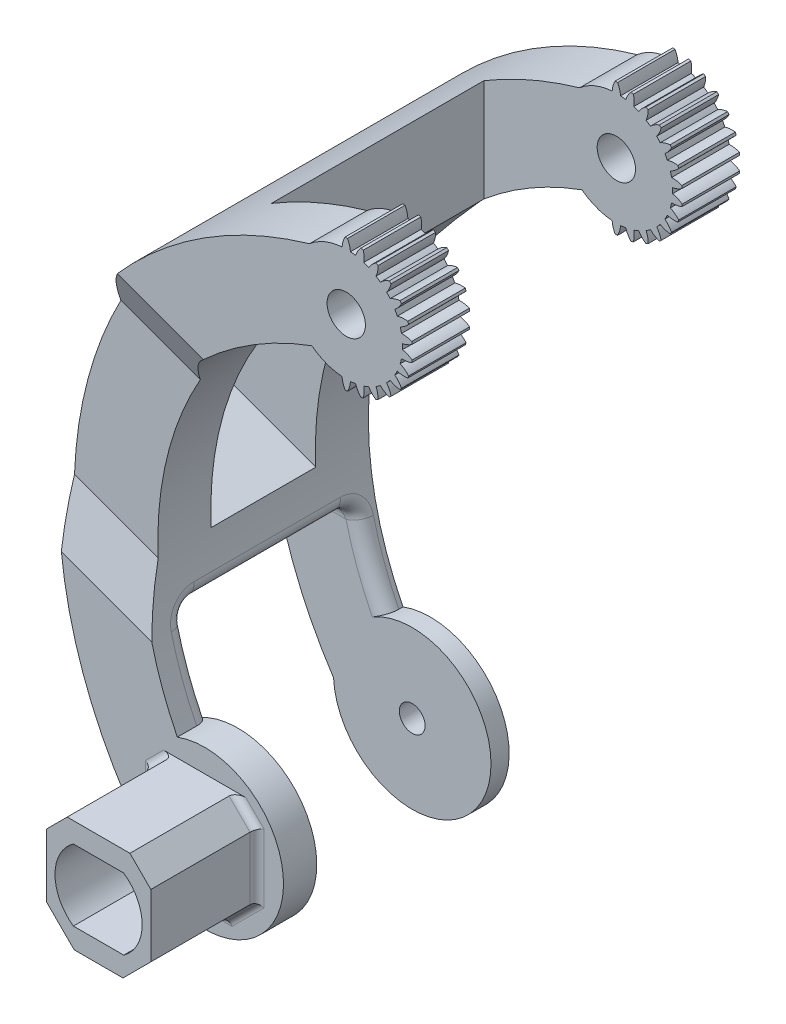
SolidWorks part; units mm, degrees
ref_plane "Alzado" through (0, 0, 0) normal (0, 0, 1) x (1, 0, 0)
ref_plane "Planta" through (0, 0, 0) normal (0, 1, 0) x (1, 0, 0)
ref_plane "Vista lateral" through (0, 0, 0) normal (1, 0, 0) x (0, 0, -1)
sketch "General" plane through (0, 0, 0) normal (0, 0, 1) x (1, 0, 0)
  line L0 (0, -33.4233) -> (0, 47689.0306) construction
  line L1 (6.6907, 0) -> (47729.1446, 0) construction
  line L2 (-11, 14) -> (-11, -14) construction
  line L3 (-23, 14) -> (23, 14) construction
  line L4 (-23, 14) -> (-23, -14) construction
  line L5 (-23, -14) -> (23, -14) construction
  line L6 (23, 14) -> (23, -14) construction
  line L7 (-23, 14) -> (23, -14) construction
  line L8 (-23, -14) -> (23, 14) construction
  line L9 (-53.8528, 23.512) -> (-38.6411, 23.4646) construction
  line L10 (-53.8528, 23.512) -> (-54.1389, 38.7648) construction
  line L11 (-53.8528, 23.512) -> (-42.0695, 24.391) construction
  line L12 (-53.8528, 23.512) -> (-42.0757, 22.5533) construction
  line L13 (-53.8528, 23.512) -> (-42.1693, 21.747) construction
  line L14 (-53.8528, 23.512) -> (-39.8274, 23.7032) construction
  line L15 (-53.8528, 23.512) -> (-39.829, 23.226) construction
  line L16 (0, -50) -> (-37.5362, -81.4966) construction
  line L103 (-42.0757, 22.5533) -> (-40.8989, 22.7984) construction
  line L104 (-39.829, 23.226) -> (-39.8274, 23.7032) construction
  line L105 (-40.8944, 24.138) -> (-42.0695, 24.391) construction
  circle A0 centre (0, -50) radius 30 construction
  circle A1 centre (-53.8528, 23.512) radius 14.0267 construction
  circle A2 centre (-53.8528, 23.512) radius 11.8161 construction
  circle A3 centre (-53.8528, 23.512) radius 12.9735 construction
  circle A4 centre (-11, 0) radius 11 construction
  circle A5 centre (11, 0) radius 11 construction
  circle A6 centre (-37.5362, -81.4966) radius 19 construction
  arc A109 (-42.1693, 21.747) -> (-42.0757, 22.5533) centre (-53.8528, 23.512) ccw construction
  arc A110 (-40.8989, 22.7984) -> (-39.829, 23.226) centre (-41.5742, 26.0406) ccw construction
  arc A111 (-39.8274, 23.7032) -> (-40.8944, 24.138) centre (-41.5916, 20.9005) ccw construction
  arc A112 (-42.0695, 24.391) -> (-42.1576, 25.198) centre (-53.8528, 23.512) ccw construction
  point P30 (0, 0)
  dimension "D1" = 60
  dimension "D8" = 23.6322
  dimension "D9" = 25.947
  dimension "D10" = 28.0535
  dimension "D12" = 22
  dimension "D13" = 38
  dimension "D2" = 50
  dimension "D3" = 28
  dimension "D4" = 12
  dimension "D5" = 46
  dimension "D6" = 12.857
  dimension "D7" = 8.92
  dimension "D11" = 4.445
  dimension "D14" = 130
sketch "dientes left" plane through (0, 0, 0) normal (0, 0, 1) x (1, 0, 0)
  line L0 (0, -33.4233) -> (0, 47689.0306) construction
  line L1 (-11, 4.2518) -> (-11, 18009.3981) construction
  line L2 (-52.3069, -19.6337) -> (-41.0879, -19.8625) construction
  line L9 (-53.8528, 23.512) -> (-38.6411, 23.4646) construction
  line L10 (35.2249, 36.7395) -> (32.3069, 26.491) construction
  line L11 (-53.8528, 23.512) -> (-42.0695, 24.391) construction
  line L12 (-53.8528, 23.512) -> (-42.0757, 22.5533) construction
  line L13 (-53.8528, 23.512) -> (-42.1693, 21.747) construction
  line L14 (-53.8528, 23.512) -> (-39.8274, 23.7032) construction
  line L15 (-53.8528, 23.512) -> (-39.829, 23.226) construction
  line L16 (-41.9402, -19.1329) -> (-42.8803, -18.9305) construction
  line L17 (-52.3069, -19.6337) -> (-52.5358, -7.4315) construction
  line L18 (-52.3069, -19.6337) -> (-42.8803, -18.9305) construction
  line L19 (-52.3069, -19.6337) -> (-41.0866, -19.4807) construction
  line L20 (-42.8852, -20.4007) -> (-41.9438, -20.2046) construction
  line L21 (-52.3069, -19.6337) -> (-40.1376, -19.6716) construction
  line L22 (-41.0879, -19.8625) -> (-41.0866, -19.4807) construction
  line L23 (-52.3069, -19.6337) -> (-42.9601, -21.0457) construction
  line L24 (-52.3069, -19.6337) -> (-42.8852, -20.4007) construction
  line L25 (-11, -8.8667) -> (-7.1144, -7.4524) construction
  line L26 (-11, -8.8667) -> (-14.6616, -7.5339) construction
  line L28 (-11, 0) -> (-11, 9.5) construction
  line L29 (-11, 0) -> (-13.8497, -7.8295) construction
  line L33 (-11, 0) -> (-8.1503, -7.8295) construction
  line L34 (-11, -8.8667) -> (-5.7586, -8.8667) construction
  line L35 (-11.4974, -8.6856) -> (-10.5026, -8.6856) construction
  line L103 (-42.0757, 22.5533) -> (-40.8989, 22.7984) construction
  line L104 (-39.829, 23.226) -> (-39.8274, 23.7032) construction
  line L105 (-40.8944, 24.138) -> (-42.0695, 24.391) construction
  line L106 (32.3069, 26.491) -> (37.8505, 37.0466) construction
  line L107 (32.3069, 26.491) -> (37.6564, 34.9915) construction
  line L108 (37.6564, 34.9915) -> (37.934, 35.9748) construction
  line L109 (37.8505, 37.0466) -> (38.032, 36.9492) construction
  line L110 (32.3069, 26.491) -> (42.3228, 27.2382) construction
  line L111 (32.3069, 26.491) -> (32.0638, 39.4559) construction
  line L112 (32.3069, 26.491) -> (42.2379, 24.9907) construction
  line L113 (36.9768, 35.383) -> (37.6564, 34.9915) construction
  line L114 (32.3069, 26.491) -> (38.032, 36.9492) construction
  line L115 (-11, 14) -> (-11, -14) construction
  circle A1 centre (-53.8528, 23.512) radius 14.0267 construction
  circle A2 centre (-53.8528, 23.512) radius 11.8161 construction
  circle A3 centre (-53.8528, 23.512) radius 12.9735 construction
  arc A7 (-41.0866, -19.4807) -> (-41.9402, -19.1329) centre (-42.498, -21.7229) ccw construction
  circle A8 centre (-52.3069, -19.6337) radius 11.2214 construction
  arc A9 (-42.8803, -18.9305) -> (-42.9508, -18.2849) centre (-52.3069, -19.6337) ccw construction
  circle A10 centre (-52.3069, -19.6337) radius 10.3788 construction
  arc A11 (-42.9601, -21.0457) -> (-42.8852, -20.4007) centre (-52.3069, -19.6337) ccw construction
  arc A12 (-41.9438, -20.2046) -> (-41.0879, -19.8625) centre (-42.484, -17.6108) ccw construction
  circle A13 centre (-52.3069, -19.6337) radius 9.4529 construction
  circle A17 centre (-11, 0) radius 8.8667 construction
  circle A20 centre (-11, 0) radius 8.075
  circle A47 centre (32.3069, 26.491) radius 11.0275 construction
  arc A48 (37.934, 35.9748) -> (38.032, 36.9492) centre (35.2249, 36.7395) ccw construction
  circle A49 centre (32.3069, 26.491) radius 11.9227 construction
  circle A50 centre (32.3069, 26.491) radius 10.0437 construction
  arc A109 (-42.1693, 21.747) -> (-42.0757, 22.5533) centre (-53.8528, 23.512) ccw construction
  arc A110 (-40.8989, 22.7984) -> (-39.829, 23.226) centre (-41.5742, 26.0406) ccw construction
  arc A111 (-39.8274, 23.7032) -> (-40.8944, 24.138) centre (-41.5916, 20.9005) ccw construction
  arc A112 (-42.0695, 24.391) -> (-42.1576, 25.198) centre (-53.8528, 23.512) ccw construction
  arc A113 (-11.598, -8.0528) -> (-11.1753, -9.4984) centre (-8.1503, -7.8295) ccw
  arc A115 (-10.8247, -9.4984) -> (-10.402, -8.0528) centre (-13.8497, -7.8295) ccw
  circle A116 centre (-11, 0) radius 9.5
  point P54 (32.3206, 26.4908)
  point P195 (-10.9863, -0.0002)
  point P220 (-11, 0)
  dimension "D8" = 23.6322
  dimension "D9" = 25.947
  dimension "D10" = 28.0535
  dimension "D2" = 16.15
  dimension "D3" = 17.7333
  dimension "D4" = 19
  dimension "D6" = 12.857
  dimension "D7" = 8.92
  dimension "D11" = 4.445
  dimension "D12" = 0.99
  dimension "D13" = 4.475
  dimension "D14" = 11.815
  dimension "D15" = 10.6558
  dimension "D5" = 20
  dimension "D16" = 20
  dimension "D17" = 0.9948
sketch "Cilindro" plane through (0, 0, 0) normal (0, 0, 1) x (1, 0, 0)
  circle A0 centre (-11, 0) radius 8.075
  dimension "D1" = 16.15
extrude "Saliente-Extruir2" add sketch "Cilindro" along normal mid plane 47
extrude "Saliente-Extruir3" add sketch "dientes left" along normal through all and the other way through all contours A116 A115 A20 A113 region at (-11, -8.6709, 0)
pattern_circular "CirPattern1" count 14 over 180 about axis through (-11, 0, 23.5) along (0, 0, 1) of "Saliente-Extruir3"
sketch "Croquis5" plane through (0, 0, 0) normal (0, 0, 1) x (1, 0, 0)
  line L0 (-11, 14) -> (-11, -14) construction
  line L1 (-16.2713, 6.1171) -> (-11, -4.8934)
  arc A0 (-11, -4.8934) -> (-41.4607, -70.8953) centre (0, -50) ccw
  arc A1 (-16.2713, 6.1171) -> (-48.8248, -82.094) centre (0, -50) ccw
  circle A2 centre (-37.5362, -81.4966) radius 11.3044 construction
  circle A3 centre (-37.5362, -81.4966) radius 1.8517
  arc A4 (-48.8248, -82.094) -> (-41.4607, -70.8953) centre (-37.5362, -81.4966) ccw
  arc A6 (-11.598, 8.0528) -> (-11.598, -8.0528) centre (-11, 0) ccw construction
  dimension "D1" = 12
extrude "Saliente-Extruir4" add sketch "Croquis5" along normal up to surface and the other way up to surface up to face at (-5.9627, 0, 23.5) other way up to face at (-5.9627, 0, -23.5)
sketch "Croquis10" plane through (0, 0, 23.5) normal (0, 0, 1) x (1, 0, 0)
  circle A0 centre (-11, 0) radius 2.75
  dimension "D1" = 5.5
extrude "Cortar-Extruir5" cut sketch "Croquis10" against normal through all and the other way blind 10
sketch "Croquis6" plane through (0, 0, 0) normal (0, 1, 0) x (1, 0, 0)
  line L1 (-30, -15.25) -> (30, -15.25)
  line L2 (-30, -15.25) -> (-30, 15.25)
  line L3 (-30, 15.25) -> (30, 15.25)
  line L4 (30, -15.25) -> (30, 15.25)
  line L5 (-30, -15.25) -> (30, 15.25) construction
  line L6 (-30, 15.25) -> (30, -15.25) construction
  point P0 (0, 0)
  dimension "D1" = 60
  dimension "D2" = 30.5
extrude "Cortar-Extruir1" cut sketch "Croquis6" against normal up to next and the other way up to next
sketch "Croquis7" plane through (0, 0, 0) normal (1, 0, 0) x (0, 0, -1)
  line L0 (0, -62.4966) -> (0, -100.4966) construction
  line L1 (-12.5, -103.4966) -> (12.5, -103.4966)
  line L2 (-12.5, -103.4966) -> (-12.5, -59.4966)
  line L3 (-12.5, -59.4966) -> (12.5, -59.4966)
  line L4 (12.5, -103.4966) -> (12.5, -59.4966)
  line L5 (-12.5, -103.4966) -> (12.5, -59.4966) construction
  line L6 (-12.5, -59.4966) -> (12.5, -103.4966) construction
  point P0 (0, -81.4966)
  dimension "D1" = 25
  dimension "D2" = 44
extrude "Cortar-Extruir2" cut sketch "Croquis7" against normal through all both
ref_plane "Plano1" through (-17.2676, 6.3516, 0) normal (-0.9385, 0.3452, 0) x (0, 0, 1)
sketch "Croquis8" plane through (-17.2676, 6.3516, 0) normal (-0.9385, 0.3452, 0) x (0, 0, 1)
  line L0 (23.5, -25.8151) -> (15.1, -39.2848)
  line L1 (23.5, -93.9023) -> (23.5, 0.1238) construction
  line L2 (15.1, -39.2848) -> (15.1, -65)
  line L3 (15.1, -65) -> (17.2723, -72.7413)
  line L4 (17.2723, -72.7413) -> (23.5, -72.7413)
  line L5 (23.5, -72.7413) -> (23.5, -25.8151)
  line L6 (0, 0) -> (0, -50000) construction
  line L8 (-23.5, -72.7413) -> (-23.5, -25.8151)
  line L11 (-15.1, -39.2848) -> (-15.1, -65)
  line L12 (-23.5, -25.8151) -> (-15.1, -39.2848)
  line L13 (-23.5, -100.749) -> (-15.1, -100.749)
  line L14 (-15.1, -65) -> (-15.1, -100.749)
  line L15 (-12.5, -75.7413) -> (12.5, -75.7413) construction
  line L17 (-23.5, -100.749) -> (-23.5, -72.7413)
  line L18 (-23.5, -100.749) -> (-12.5, -100.749) construction
  line L19 (-7.5, -35) -> (7.5, -35)
  line L20 (-7.5, -35) -> (-7.5, -65)
  line L21 (-7.5, -65) -> (7.5, -65)
  line L22 (7.5, -35) -> (7.5, -65)
  line L23 (-7.5, -35) -> (7.5, -65) construction
  line L24 (-7.5, -65) -> (7.5, -35) construction
  point P13 (0, -50)
  point P20 (20.3862, -72.7413)
  dimension "D1" = 15
  dimension "D2" = 30
  dimension "D3" = 50
  dimension "D4" = 8.4
  dimension "D5" = 3
extrude "Cortar-Extruir3" cut sketch "Croquis8" along normal through all both and the other way through all
sketch "Croquis9" plane through (0, 0, 23.5) normal (0, 0, 1) x (1, 0, 0)
  circle A0 centre (-37.5362, -81.4966) radius 11.2842
  circle A1 centre (-37.5362, -81.4966) radius 46.3237
  circle M1 centre (-37.5362, -81.4966) radius 1.8517
  arc M2 (-41.4607, -70.8953) -> (-45.1293, -60.9062) centre (0, -50) cw
  line M3 (-45.1293, -60.9062) -> (-58.1057, -56.133)
  arc M4 (-58.1057, -56.133) -> (-48.8248, -82.094) centre (0, -50) ccw
  arc M8 (-48.8248, -82.094) -> (-41.4607, -70.8953) centre (-37.5362, -81.4966) ccw
extrude "Cortar-Extruir4" cut sketch "Croquis9" against normal up to vertex (6.2277 mm away) contours A0 M2 M3 M4 | A0 M2 M4 M8 M1 region at (-48.5012, -81.4966, 23.5) region at (-50.1178, -67.3217, 23.5) up to point (-58.1057, -56.133, 17.2723)
sketch "Sketch9" plane through (0, 0, 0) normal (0, 0, 1) x (1, 0, 0)
  line L1 (-45.0362, -73.4966) -> (-30.0362, -73.4966)
  line L2 (-45.0362, -73.4966) -> (-45.0362, -89.4966)
  line L3 (-45.0362, -89.4966) -> (-30.0362, -89.4966)
  line L4 (-30.0362, -73.4966) -> (-30.0362, -89.4966)
  line L5 (-45.0362, -73.4966) -> (-30.0362, -89.4966) construction
  line L6 (-45.0362, -89.4966) -> (-30.0362, -73.4966) construction
  point P0 (-37.5362, -81.4966)
  dimension "D1" = 16
  dimension "D2" = 15
extrude "Boss-Extrude2" add sketch "Sketch9" along normal blind 20 from surface starting at face at (-35.6844, -81.4966, 12.5)
sketch "Sketch10" plane through (0, 0, 12.5) normal (0, 0, 1) x (1, 0, 0)
  line L1 (-43.8362, -76.3966) -> (-31.2362, -76.3966)
  line L2 (-43.8362, -76.3966) -> (-43.8362, -86.5966)
  line L3 (-43.8362, -86.5966) -> (-31.2362, -86.5966)
  line L4 (-31.2362, -76.3966) -> (-31.2362, -86.5966)
  line L5 (-43.8362, -76.3966) -> (-31.2362, -86.5966) construction
  line L6 (-43.8362, -86.5966) -> (-31.2362, -76.3966) construction
  point P0 (-37.5362, -81.4966)
  dimension "D1" = 10.2
  dimension "D2" = 12.6
extrude "Cut-Extrude8" cut sketch "Sketch10" along normal blind 6 from offset 4
sketch "Sketch11" plane through (0, 0, 0) normal (0, 0, 1) x (1, 0, 0)
  line L1 (-43.6362, -76.3966) -> (-31.4362, -76.3966)
  line L2 (-43.6362, -76.3966) -> (-43.6362, -86.5966)
  line L3 (-43.6362, -86.5966) -> (-31.4362, -86.5966)
  line L4 (-31.4362, -76.3966) -> (-31.4362, -86.5966)
  line L5 (-43.6362, -76.3966) -> (-31.4362, -86.5966) construction
  line L6 (-43.6362, -86.5966) -> (-31.4362, -76.3966) construction
  point P0 (-37.5362, -81.4966)
  dimension "D1" = 10.2
  dimension "D2" = 12.2
extrude "Cut-Extrude10" cut sketch "Sketch11" along normal blind 6 from surface starting at face at (-44.4725, -70.9472, 12.5)
sketch "Sketch12" plane through (0, 0, 32.5) normal (0, 0, 1) x (1, 0, 0)
  line L1 (-41.149, -76.3966) -> (-33.9234, -76.3966)
  line L3 (-41.149, -86.5966) -> (-33.9234, -86.5966)
  arc A0 (-41.149, -76.3966) -> (-41.149, -86.5966) centre (-37.5362, -81.4966) ccw
  arc A1 (-33.9234, -86.5966) -> (-33.9234, -76.3966) centre (-37.5362, -81.4966) ccw
  point P0 (-37.5362, -81.4966)
  dimension "D2" = 12.5
  dimension "D1" = 5.1
  dimension "D3" = 5.1
extrude "Cut-Extrude11" cut sketch "Sketch12" against normal up to next
sketch "Sketch14" plane through (0, 0, 0) normal (0, 1, 0) x (1, 0, 0)
  line L0 (-45.0362, -32.5) -> (-45.0362, -17.2723) construction
  line L1 (-42.0362, -12.5) -> (-32.0362, -12.5)
  line L2 (-42.0362, -12.5) -> (-42.0362, -32.5)
  line L3 (-42.0362, -32.5) -> (-32.0362, -32.5)
  line L4 (-32.0362, -12.5) -> (-32.0362, -32.5)
  line L5 (-42.0362, -12.5) -> (-32.0362, -32.5) construction
  line L6 (-42.0362, -32.5) -> (-32.0362, -12.5) construction
  line L7 (-45.0362, -32.5) -> (-30.0362, -32.5) construction
  point P0 (-37.0362, -22.5)
  dimension "D1" = 10
  dimension "D2" = 20
  dimension "D3" = 3
  dimension "D4" = 0
chamfer "Chamfer1" distance 3 angle 45 2 edges at (-30.0362, -73.4966, 24.8862) (-45.0362, -73.4966, 24.8862)
chamfer "Chamfer2" distance 4 angle 45 2 edges at (-30.0362, -89.4966, 24.8862) (-45.0362, -89.4966, 24.8862)
fillet "Fillet1" radius 1 7 edges at (-43.0362, -87.4966, 17.2723) (-45.0362, -80.9966, 17.2723) (-43.5362, -74.9966, 17.2723) (-31.5362, -74.9966, 17.2723) (-30.0362, -80.9966, 17.2723) (-32.0362, -87.4966, 17.2723) (-37.5362, -89.4966, 17.2723)
fillet "Fillet2" radius 2 5 edges at (-43.8259, -65.3261, 12.5) (-43.8259, -65.3261, -12.5) (-45.4468, -59.4966, 0) (-51.5492, -59.4966, -12.5) (-51.5492, -59.4966, 12.5)
sketch "Sketch15" plane through (0, 0, 0) normal (0, 0, 1) x (1, 0, 0)
  line L0 (-66.1604, 18.1072) -> (12.5164, 18.1072)
  line L1 (-66.1604, 18.1072) -> (-66.1604, -102.575)
  line L2 (12.5164, 18.1072) -> (12.5164, -102.575)
  line L3 (-66.1604, -102.575) -> (12.5164, -102.575)
sketch "Sketch16" plane through (0, 0, 0) normal (0, 0, 1) x (1, 0, 0)
  circle A0 centre (-37.5362, -81.4966) radius 3.5
  circle A1 centre (-37.5362, -81.4966) radius 1.8517
  dimension "D1" = 7
extrude "Boss-Extrude3" add sketch "Sketch16" against normal blind 2 from surface starting at face at (-37.5362, -79.6449, -15.1)
fillet "Fillet3" radius 2 1 edges at (-37.5362, -77.9966, -15.1)
equation "\"Z\"= 28"
equation "\"De\"= 19"
equation "\"M\" = \"De\" / ( \"Z\" + 2 )"
equation "\"Dp\"= \"M\" * \"Z\""
equation "\"e\"= \"M\" * 3.1416 / 2"
equation "\"X\" = 0"
equation "\"alpha\"= 20"
equation "\"Din\"= \"Dp\" - ( 2 * \"M\" * 1.25 )"
equation "\"D2@dientes left\"=\"Din\""
equation "\"D3@dientes left\"=\"Dp\""
equation "\"D5@dientes left\"=\"alpha\""
equation "\"D16@dientes left\"=\"alpha\""
equation "\"D17@dientes left\"=\"e\"-\"X\""
equation "\"D4@dientes left\"=\"De\""
